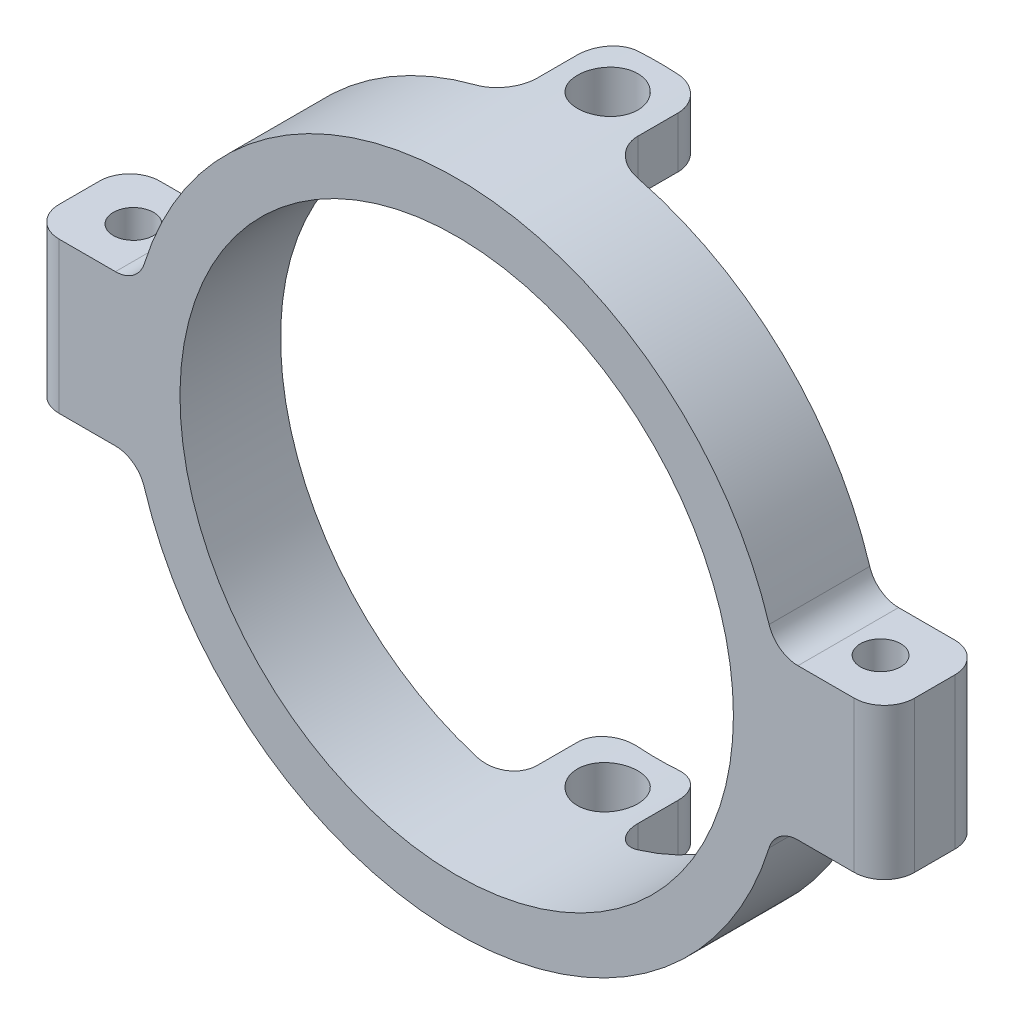
SolidWorks part; units mm, degrees
ref_plane "Alzado" through (0, 0, 0) normal (0, 0, 1) x (1, 0, 0)
ref_plane "Planta" through (0, 0, 0) normal (0, 1, 0) x (1, 0, 0)
ref_plane "Vista lateral" through (0, 0, 0) normal (1, 0, 0) x (0, 0, -1)
sketch "Croquis1" plane through (0, 0, 0) normal (0, 0, 1) x (1, 0, 0)
  circle A0 centre (0, 0) radius 27.5
  circle A1 centre (0, 0) radius 32.5
  dimension "D1" = 55
  dimension "D2" = 5
extrude "Saliente-Extruir1" add sketch "Croquis1" along normal blind 10
sketch "Croquis2" plane through (0, 0, 10) normal (0, 0, 1) x (1, 0, 0)
  line L0 (42.5, 7.5) -> (42.5, -7.5)
  line L1 (42.5, -7.5) -> (31.6228, -7.5)
  line L2 (31.6228, 7.5) -> (42.5, 7.5)
  line L3 (0, 10.498) -> (0, -9.1129) construction
  line L4 (-31.6228, 7.5) -> (-42.5, 7.5)
  line L5 (-42.5, 7.5) -> (-42.5, -7.5)
  line L6 (-42.5, -7.5) -> (-31.6228, -7.5)
  circle A0 centre (0, 0) radius 32.5 construction
  arc A2 (31.6228, 7.5) -> (31.6228, -7.5) centre (0, 0) cw
  arc A3 (-31.6228, 7.5) -> (-31.6228, -7.5) centre (0, 0) ccw
  point P7 (32.5, 0)
  point P8 (42.5, 0)
  dimension "D1" = 10
  dimension "D2" = 15
extrude "Saliente-Extruir2" add sketch "Croquis2" against normal blind 10
ref_plane "Plano1" through (0, 0, 0) normal (1, 0, 0) x (0, 0, -1)
sketch "Croquis3" plane through (0, -7.5, 0) normal (0, -1, 0) x (1, 0, 0)
  line L0 (42.5, 0) -> (42.5, 10) construction
  line L1 (31.6228, 0) -> (42.5, 0) construction
  line L2 (0, -5.5) -> (0, 5.5) construction
  circle A0 centre (37.1212, 5) radius 2
  circle A1 centre (-37.1212, 5) radius 2
  dimension "D1" = 4
  dimension "D2" = 5.3788
  dimension "D3" = 5
extrude "Cortar-Extruir1" cut sketch "Croquis3" against normal through all
sketch "Croquis4" plane through (0, 0, 0) normal (0, 0, -1) x (-1, 0, 0)
  line L0 (-5, -27.0416) -> (-5, -32.1131)
  line L1 (5, -27.0416) -> (5, -32.1131)
  line L2 (0, 0) -> (15.6938, 0) construction
  line L3 (-5, 27.0416) -> (-5, 32.1131)
  line L4 (5, 27.0416) -> (5, 32.1131)
  circle A0 centre (0, 0) radius 27.5 construction
  arc A1 (-5, -27.0416) -> (5, -27.0416) centre (0, 0) ccw
  arc A2 (-31.6228, -7.5) -> (31.6228, -7.5) centre (0, 0) ccw construction
  arc A3 (-5, -32.1131) -> (5, -32.1131) centre (0, 0) ccw
  arc A4 (-5, 27.0416) -> (5, 27.0416) centre (0, 0) cw
  arc A5 (-5, 32.1131) -> (5, 32.1131) centre (0, 0) cw
  point P6 (0, -27.5)
  dimension "D1" = 10
extrude "Saliente-Extruir3" add sketch "Croquis4" along normal blind 10
ref_plane "Plano2" through (0, -32.5, 0) normal (0, -1, 0) x (-1, 0, 0)
sketch "Croquis5" plane through (0, -32.5, 0) normal (0, -1, 0) x (-1, 0, 0)
  line L0 (-5, 10) -> (-5, 0) construction
  line L2 (5, 10) -> (-5, 10) construction
  circle A0 centre (0, 5) radius 3
  dimension "D1" = 6
  dimension "D2" = 5
  dimension "D3" = 5
extrude "Cortar-Extruir2" cut sketch "Croquis5" against normal through all
fillet "Redondeo2" radius 3 16 edges at (31.6228, 7.5, 5) (31.6228, -7.5, 5) (-5, 29.5774, -10) (5, 29.5774, -10) (5, 29.5774, 0) (42.5, 0, 10) (42.5, 0, 0) (-31.6228, 7.5, 5) (5, -29.5774, 0) (-5, -29.5774, -10) (5, -29.5774, -10) (-42.5, 0, 10) (-42.5, 0, 0) (-31.6228, -7.5, 5) (-5, 29.5774, 0) (-5, -29.5774, 0)
